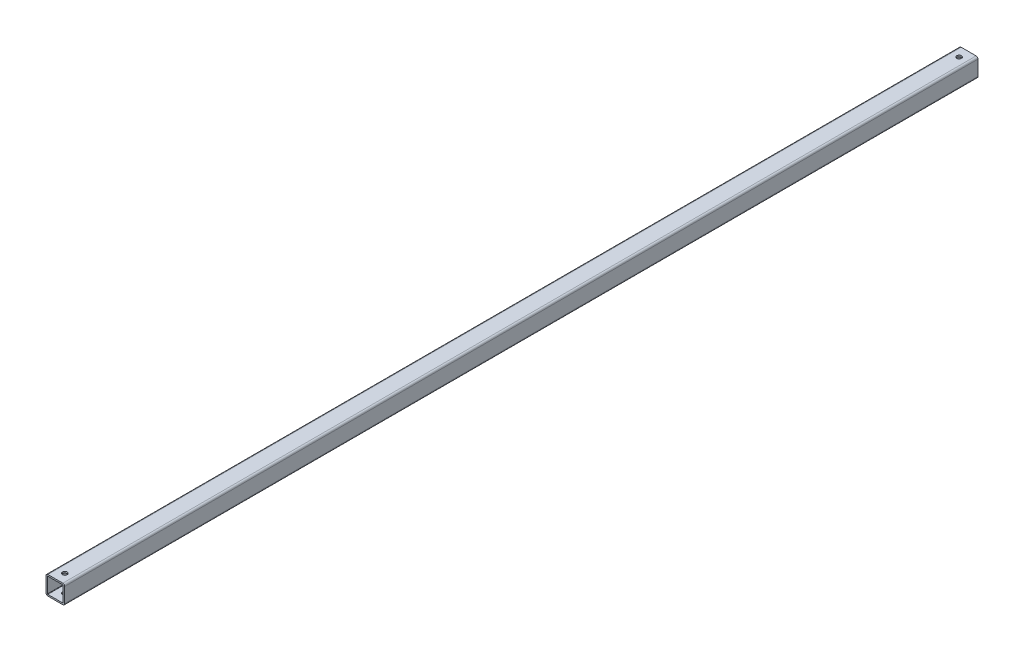
SolidWorks part; units mm, degrees
material "6063-T4"
ref_plane "Front Plane" through (0, 0, 0) normal (0, 0, 1) x (1, 0, 0)
ref_plane "Top Plane" through (0, 0, 0) normal (0, 1, 0) x (1, 0, 0)
ref_plane "Right Plane" through (0, 0, 0) normal (1, 0, 0) x (0, 0, -1)
sketch "Sketch1" plane through (0, 0, 0) normal (0, 0, 1) x (1, 0, 0)
  line L1 (10, -12.5) -> (-10, -12.5)
  line L2 (12.5, -10) -> (12.5, 10)
  line L3 (10, 12.5) -> (-10, 12.5)
  line L4 (-12.5, -10) -> (-12.5, 10)
  line L5 (12.5, -12.5) -> (-12.5, 12.5) construction
  line L6 (12.5, 12.5) -> (-12.5, -12.5) construction
  arc A0 (-10, 12.5) -> (-12.5, 10) centre (-10, 10) ccw
  arc A1 (12.5, 10) -> (10, 12.5) centre (10, 10) ccw
  arc A2 (10, -12.5) -> (12.5, -10) centre (10, -10) ccw
  arc A3 (-10, -12.5) -> (-12.5, -10) centre (-10, -10) cw
  point P0 (0, 0)
  dimension "D2" = 2.5
  dimension "D1" = 25
extrude "Extrude-Thin1" add sketch "Sketch1" along normal mid plane 1219.2 thin thin type one direction reverse wall 2
hole_wizard "1/4 (0.25) Diameter Hole1" positions "Sketch2" profile "Sketch3" hole size "1/4" standard "ANSI Inch"
sketch "Sketch2" plane through (0, 12.5, 0) normal (0, 1, 0) x (1, 0, 0)
  point P0 (0, 596.9)
  point P3 (0, -596.9)
sketch "Sketch3" plane through (0, 12.5, -596.9) normal (1, 0, 0) x (0, 0, 1)
  line L0 (0, 0) -> (0, 29.8477)
  line L1 (0, 29.8477) -> (3.175, 27.94)
  line L2 (3.175, 27.94) -> (3.175, 0)
  line L5 (3.175, 0) -> (0, 0)
  line L10 (0, 29.8477) -> (-3.175, 27.94) construction
  line L11 (0, -6.35) -> (0, 107.95) construction
  dimension "Hole Dia." = 6.35
  dimension "Hole Depth" = 27.94
  dimension "Drill Angle" = 118
equation "\"D2@Sketch1\" = \"D5@Extrude-Thin1\" * 1.25"
